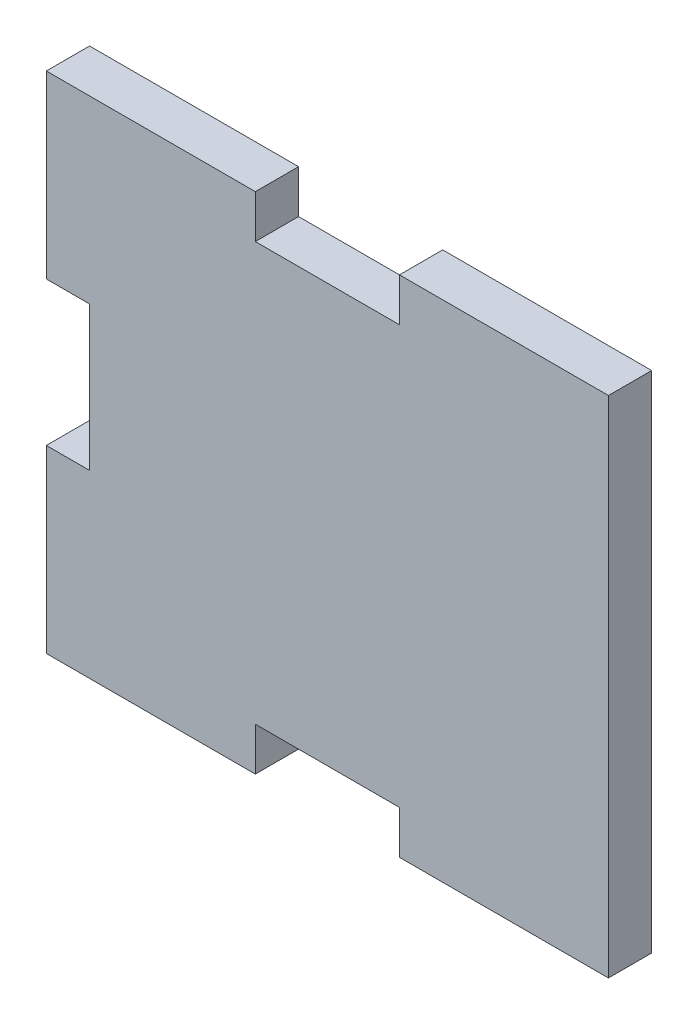
SolidWorks part; units mm, degrees
material "MDF"
ref_plane "Plano frontal" through (0, 0, 0) normal (0, 0, 1) x (1, 0, 0)
ref_plane "Plano superior" through (0, 0, 0) normal (0, 1, 0) x (1, 0, 0)
ref_plane "Plano direito" through (0, 0, 0) normal (1, 0, 0) x (0, 0, -1)
sketch "Esboço1" plane through (0, 0, 0) normal (0, 0, 1) x (1, 0, 0)
  line L0 (-19.5, 0) -> (19.5, 0) construction
  line L1 (-19.5, -17.5) -> (19.5, -17.5)
  line L2 (-19.5, -17.5) -> (-19.5, 17.5)
  line L3 (-19.5, 17.5) -> (19.5, 17.5)
  line L4 (19.5, -17.5) -> (19.5, 17.5)
  line L5 (-19.5, -17.5) -> (19.5, 17.5) construction
  line L6 (-19.5, 17.5) -> (19.5, -17.5) construction
  line L7 (5, 14.5) -> (-5, 14.5)
  line L8 (5, 14.5) -> (5, 17.5)
  line L9 (5, 17.5) -> (-5, 17.5)
  line L10 (-5, 14.5) -> (-5, 17.5)
  line L11 (5, 14.5) -> (-5, 17.5) construction
  line L12 (5, 17.5) -> (-5, 14.5) construction
  line L13 (5, -17.5) -> (-5, -17.5)
  line L14 (-5, -14.5) -> (-5, -17.5)
  line L15 (5, -14.5) -> (-5, -14.5)
  line L16 (5, -14.5) -> (5, -17.5)
  line L17 (-19.5, 5) -> (-16.5, 5)
  line L18 (-16.5, 5) -> (-16.5, -5)
  line L19 (-16.5, -5) -> (-19.5, -5)
  line L20 (-19.5, -5) -> (-19.5, 5)
  point P0 (0, 0)
  point P6 (0, 16)
  point P13 (0, 0)
  point P14 (0, 16)
  point P15 (0, 0)
  point P20 (-16.5, 0)
  point P28 (19.5, 0)
  dimension "D5" = 3
  dimension "D1" = 35
  dimension "D2" = 10
  dimension "D3" = 10
  dimension "D4" = 3
  dimension "D8" = 14.5
extrude "Ressalto-extrusão1" add sketch "Esboço1" along normal blind 3 contours L15 L16 L1 L4 L3 L8 L7 L10 L2 L14 region at (0.4235, 0, 0)
